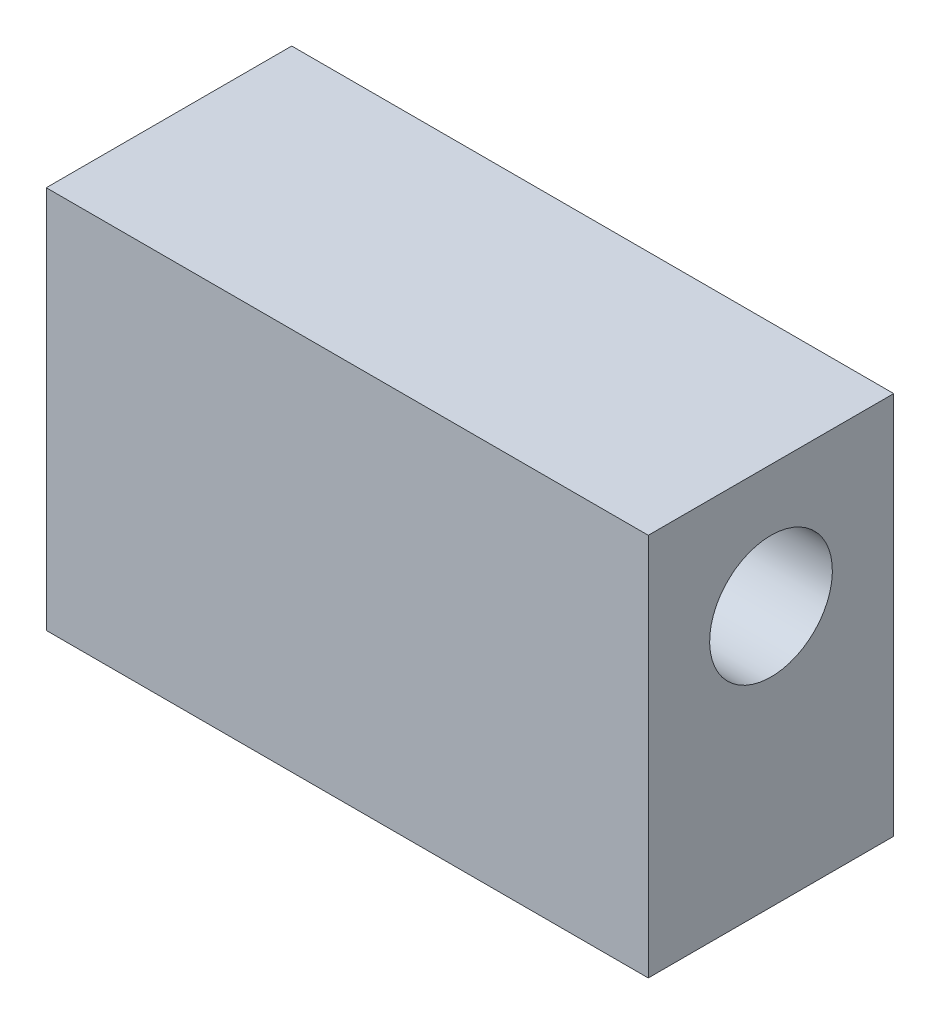
SolidWorks part; units mm, degrees
material "1060 Alloy"
ref_plane "Front" through (0, 0, 0) normal (0, 0, 1) x (1, 0, 0)
ref_plane "Top" through (0, 0, 0) normal (0, 1, 0) x (1, 0, 0)
ref_plane "Right" through (0, 0, 0) normal (1, 0, 0) x (0, 0, -1)
sketch "Sketch3" plane through (0, 0, 0) normal (0, 0, 1) x (1, 0, 0)
  line L0 (-0.127, -6.35) -> (30.1755, -6.35)
  line L1 (0, 0) -> (31.1484, 0)
  line L2 (0, 0) -> (0, -19.8376)
  line L3 (0, -19.8376) -> (31.1484, -19.8376)
  line L4 (31.1484, 0) -> (31.1484, -19.8376)
  line L5 (15.5742, -19.8376) -> (15.5742, 0) construction
  line L6 (15.5742, -6.35) -> (8.0621, -19.3614) construction
  line L15 (12.5496, -11.5887) -> (15.5742, -13.335) construction
  line L16 (15.5742, -6.35) -> (22.9274, -19.0862) construction
  circle A0 centre (15.5742, -6.35) radius 6.0492 construction
  point P14 (0, -6.35)
  point P17 (9.525, -6.35)
  point P19 (31.1484, -6.35)
  point P20 (7.7871, -19.8376)
  point P24 (23.3613, -19.8376)
  dimension "D2" = 6.35
  dimension "D6" = 3.4925
  dimension "D3" = 60
  dimension "D1" = 9.525
  dimension "D4" = 9.525
  dimension "D5" = 60
extrude "Boss-Extrude1" add sketch "Sketch3" along normal mid plane 12.7
sketch "Sketch4" plane through (0, 0, 0) normal (-1, 0, 0) x (0, 0, 1)
  circle A0 centre (0, -6.35) radius 3.175
  dimension "D1" = 6.35
extrude "Cut-Extrude1" cut sketch "Sketch4" against normal blind 9.525
ref_plane "Plane1" through (7.7871, -19.8376, 0) normal (-0.5, -0.866, 0) x (-0.866, 0.5, 0)
ref_plane "Mirror Plane" through (15.5742, 0, 0) normal (-1, 0, 0) x (0, 0, 1)
sketch "Sketch5" plane through (7.7871, -19.8376, 0) normal (-0.5, -0.866, 0) x (-0.866, 0.5, 0)
  circle A0 centre (0, 0) radius 3.175
  dimension "D1" = 6.35
extrude "Cut-Extrude5" cut sketch "Sketch5" against normal blind 9.525 and the other way up to next
sketch "Sketch6" plane through (0, 0, -6.35) normal (0, 0, -1) x (-1, 0, 0)
  circle A0 centre (-15.5742, -6.35) radius 3.175
  dimension "D1" = 6.35
extrude "Cut-Extrude6" cut sketch "Sketch6" against normal blind 9.525
mirror "Mirror1" about plane through (15.5742, 0, 0) normal (-1, 0, 0) of "Cut-Extrude1", "Cut-Extrude5"
equation "\"truss_member_od\" = .25in"
equation "\"truss_member_id\" = 0in"
equation "\"truss_member_L1\" = 2.75in"
equation "\"connector_hole_depth\" = .375in"
equation "\"D1@Boss-Extrude1\"=\"truss_member_od\"*2"
equation "\"D6@Sketch3\"=\"truss_member_od\"/2*1.1"
equation "\"D1@Sketch4\"=\"truss_member_od\""
equation "\"D1@Cut-Extrude1\"=\"connector_hole_depth\""
equation "\"D1@Sketch3\"=\"connector_hole_depth\""
equation "\"D4@Sketch3\"=\"connector_hole_depth\""
equation "\"D1@Sketch5\"=\"truss_member_od\""
equation "\"D1@Cut-Extrude5\"=\"connector_hole_depth\""
equation "\"D1@Cut-Extrude6\"=\"connector_hole_depth\""
equation "\"D1@Sketch6\"=\"truss_member_od\""
